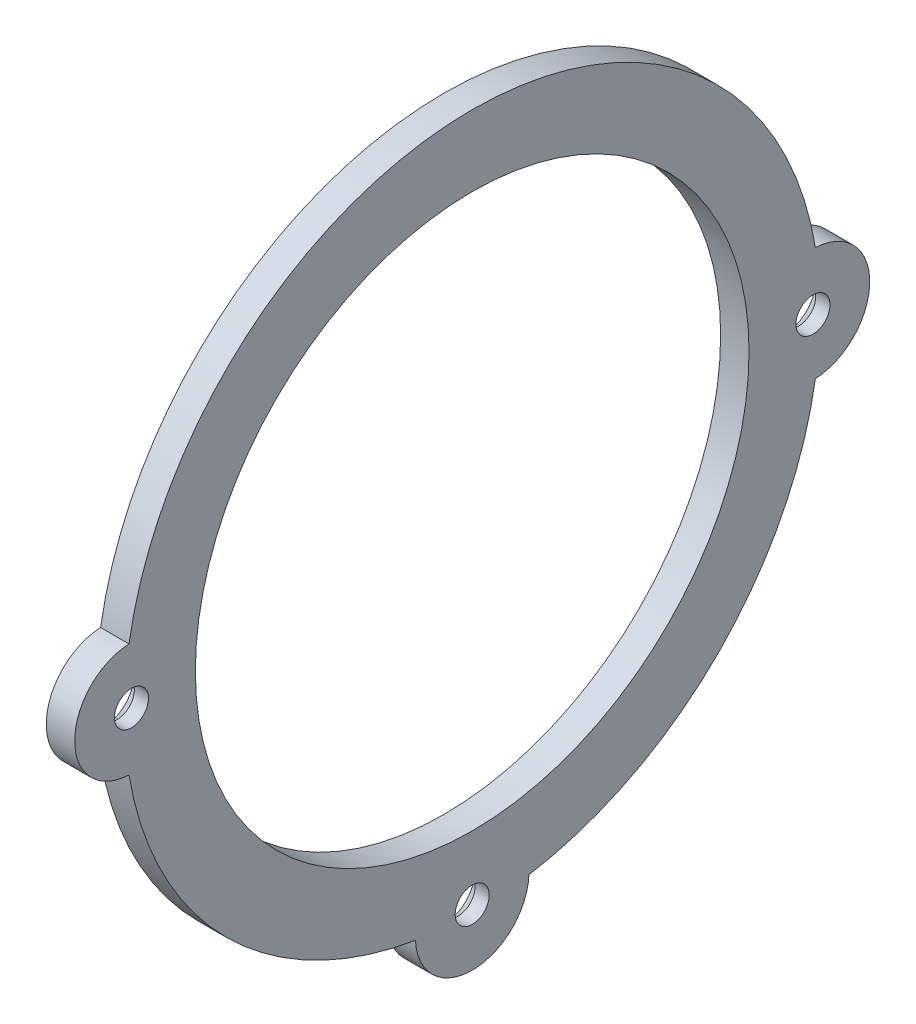
SolidWorks part; units mm, degrees
ref_plane "Спереди" through (0, 0, 0) normal (0, 0, 1) x (1, 0, 0)
ref_plane "Сверху" through (0, 0, 0) normal (0, 1, 0) x (1, 0, 0)
ref_plane "Справа" through (0, 0, 0) normal (1, 0, 0) x (0, 0, -1)
sketch "Эскиз1" plane through (0, 0, 0) normal (1, 0, 0) x (0, 0, -1)
  arc A0 (-24.1719, -3.9963) -> (-3.9963, -24.1719) centre (0, 0) ccw
  circle A1 centre (0, 0) radius 19.5
  circle A2 centre (0, 0) radius 24 construction
  arc A3 (-24.1719, 3.9963) -> (-24.1719, -3.9963) centre (-24, 0) ccw
  arc A4 (-3.9963, -24.1719) -> (3.9963, -24.1719) centre (0, -24) ccw
  arc A5 (24.1719, -3.9963) -> (24.1719, 3.9963) centre (24, 0) ccw
  arc A6 (24.1719, 3.9963) -> (-24.1719, 3.9963) centre (0, 0) ccw
  arc A7 (3.9963, -24.1719) -> (24.1719, -3.9963) centre (0, 0) ccw
  dimension "D1" = 49
  dimension "D2" = 39
  dimension "D3" = 48
  dimension "D4" = 8
extrude "Бобышка-Вытянуть1" add sketch "Эскиз1" along normal blind 2
hole_wizard "Зенковка для  винта с плоской головкой M21" positions "Эскиз3" profile "Эскиз4" countersink size "M2" standard "Ansi Metric"
sketch "Эскиз3" plane through (0, 0, 0) normal (1, 0, 0) x (0, 0, -1)
  point P0 (-24, 0)
  point P3 (0, -24)
  point P6 (24, 0)
sketch "Эскиз4" plane through (0, 0, 24) normal (0, 1, 0) x (0, 0, 1)
  line L0 (0, 0) -> (0, 5.721)
  line L1 (0, 5.721) -> (1.2, 5)
  line L2 (1.2, 5) -> (1.2, 1)
  line L3 (1.2, 1) -> (2.2, 0)
  line L5 (2.2, 0) -> (0, 0)
  line L6 (-1.2, 1) -> (-2.2, 0) construction
  line L10 (0, 5.721) -> (-1.2, 5) construction
  line L11 (0, -6.35) -> (0, 107.95) construction
  dimension "Диаметр отверстия" = 2.4
  dimension "Глубина отверстия" = 5
  dimension "Диаметр передней зенковки" = 4.4
  dimension "Угол передней зенковки" = 90
  dimension "Угол заточки сверла" = 118
